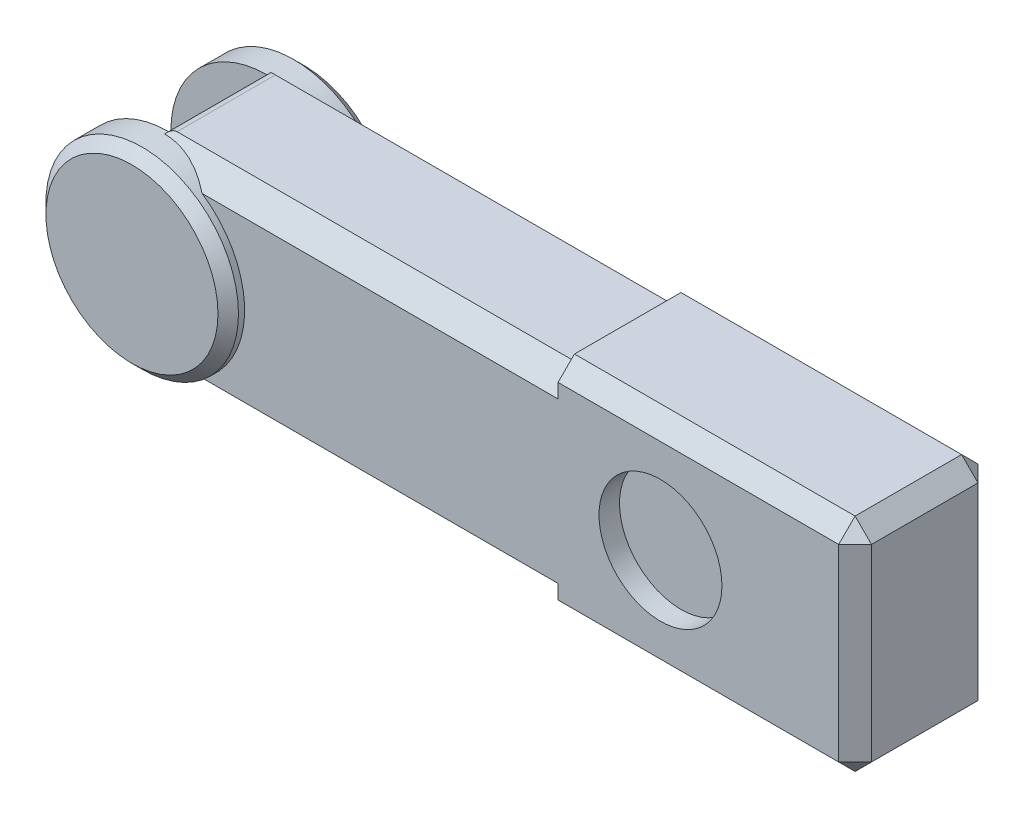
SolidWorks part; units mm, degrees
ref_plane "Plan de face" through (0, 0, 0) normal (0, 0, 1) x (1, 0, 0)
ref_plane "Plan de dessus" through (0, 0, 0) normal (0, 1, 0) x (1, 0, 0)
ref_plane "Plan de droite" through (0, 0, 0) normal (1, 0, 0) x (0, 0, -1)
sketch "Esquisse1" plane through (0, 0, 0) normal (0, 0, 1) x (1, 0, 0)
  line L0 (95, -54) -> (95, 54)
  line L1 (95, 54) -> (-50, 54)
  line L2 (-50, 54) -> (-50, 49)
  line L3 (-50, 49) -> (-250, 49)
  line L4 (-250, 0) -> (0, 0) construction
  line L5 (-250, 49) -> (-250, 47)
  line L6 (-50, -54) -> (-50, -49)
  line L7 (95, -54) -> (-50, -54)
  line L8 (-50, -49) -> (-250, -49)
  line L9 (-250, -49) -> (-250, -47)
  arc A0 (-250, 47) -> (-250, -47) centre (-250, 0) ccw
  dimension "D2" = 5
  dimension "D3" = 95
  dimension "D7" = 47
  dimension "D1" = 250
  dimension "D4" = 108
  dimension "D5" = 54
  dimension "D6" = 98
extrude "Boss.-Extru.1" add sketch "Esquisse1" along normal blind 68
sketch "Sketch3" plane through (0, 0, 68) normal (0, 0, 1) x (1, 0, 0)
  circle A0 centre (0, 0) radius 30
extrude "Cut-Extrude3" cut sketch "Sketch3" against normal blind 10
sketch "Esquisse2" plane through (0, 0, 68) normal (0, 0, 1) x (1, 0, 0)
  circle A0 centre (-250, 0) radius 47
extrude "Boss.-Extru.2" add sketch "Esquisse2" along normal blind 8
chamfer "Chanfrein1" distance 5 angle 45 1 edges at (-203, 0, 76)
sketch "Esquisse3" plane through (0, 0, 0) normal (0, 0, -1) x (-1, 0, 0)
  circle A0 centre (250, 0) radius 47
extrude "Boss.-Extru.3" add sketch "Esquisse3" along normal blind 8
chamfer "Chanfrein2" distance 5 angle 45 1 edges at (-297, 0, -8)
chamfer "Chanfrein4" distance 10 angle 45 4 edges at (-150, -49, 0) (-150, -49, 68) (-150, 49, 68) (-150, 49, 0)
ref_plane "Plane1" through (0, 0, 10) normal (0, 0, -1) x (-1, 0, 0)
ref_point "Point1"
ref_point "Point2"
sketch "Sketch2" plane through (0, 0, 10) normal (0, 0, -1) x (-1, 0, 0)
  circle A0 centre (250, 0) radius 47
extrude "Cut-Extrude2" cut sketch "Sketch2" against normal blind 48
fillet "Fillet1" radius 5 1 edges at (-250, 49, 34)
chamfer "Chamfer1" distance 8 angle 45 8 edges at (95, -54, 34) (22.5, -54, 0) (95, 0, 0) (22.5, 54, 0) (95, 54, 34) (22.5, 54, 68) (95, 0, 68) (22.5, -54, 68)
